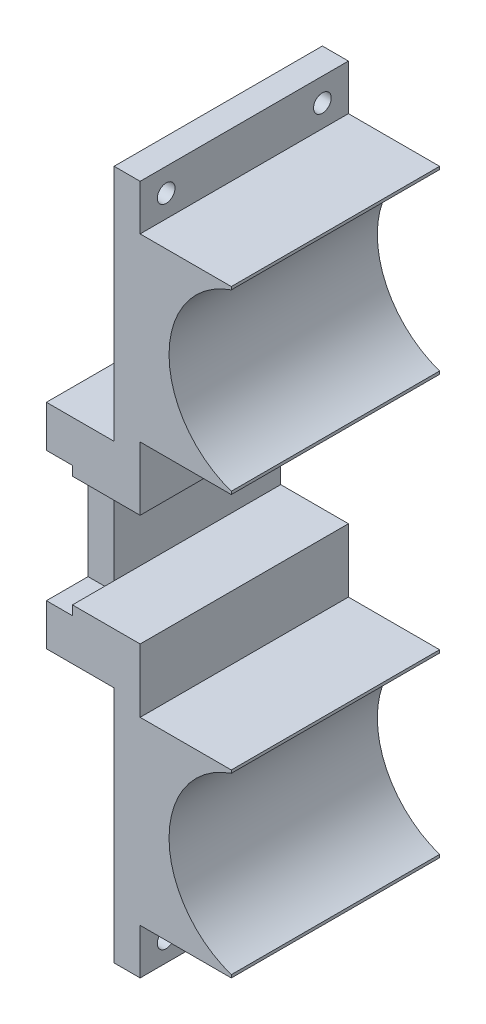
SolidWorks part; units mm, degrees
ref_plane "Płaszczyzna przednia" through (0, 0, 0) normal (0, 0, 1) x (1, 0, 0)
ref_plane "Płaszczyzna górna" through (0, 0, 0) normal (0, 1, 0) x (1, 0, 0)
ref_plane "Płaszczyzna prawa" through (0, 0, 0) normal (1, 0, 0) x (0, 0, -1)
sketch "Sketch1" plane through (0, 0, 0) normal (0, 0, 1) x (1, 0, 0)
  line L0 (0, 0) -> (0, -20.5)
  line L1 (0, -20.5) -> (13, -20.5)
  line L2 (13, -20.5) -> (13, -66.25)
  line L3 (13, -66.25) -> (18, -66.25)
  line L4 (18, -66.25) -> (18, -57.5)
  line L5 (18, -57.5) -> (37.5083, -57.5)
  line L7 (37.5083, -22.9) -> (18, -22.9)
  line L8 (18, -22.9) -> (18, -10.7)
  line L9 (18, -10.7) -> (5, -10.7)
  line L10 (5, -10.7) -> (5, 0)
  line L11 (5, 0) -> (0, 0)
  line L12 (35.5083, -22.9) -> (35.5083, -23.4571)
  line L13 (35.5083, -56.9429) -> (35.5083, -57.5)
  arc A0 (37.5083, -22.9) -> (37.5083, -57.5) centre (41.25, -40.2) ccw
  dimension "D10" = 19.5083
  dimension "D5" = 17.7
  dimension "D1" = 10.7
  dimension "D2" = 13
  dimension "D3" = 12.2
  dimension "D4" = 28.25
  dimension "D6" = 5
  dimension "D7" = 5
  dimension "D8" = 20.5
  dimension "D9" = 45.75
  dimension "D11" = 34.6
  dimension "D12" = 2
extrude "Boss-Extrude1" add sketch "Sketch1" along normal blind 40 contours A0 L12 L7 L8 L9 L10 L11 L0 L1 L2 L3 L4 L5 L13 region at (16.2423, -33.1042, 0)
mirror "Mirror1" about plane through (0, 0, 0) normal (0, 1, 0) of "Boss-Extrude1"
sketch "Sketch3" plane through (13, 0, 0) normal (-1, 0, 0) x (0, 0, 1)
  point P0 (35, -62.175)
  point P1 (5, -62.175)
  point P3 (35, 61.775)
  point P5 (5, 61.775)
hole_wizard "M3 Clearance Hole1" positions "Sketch3" profile "Sketch5" hole size "M3" standard "DIN" end condition up to next
sketch "Sketch5" plane through (13, -62.175, 35) normal (0, 1, 0) x (0, 0, 1)
  line L0 (0, 0) -> (0, 5)
  line L1 (0, 5) -> (1.7, 5)
  line L2 (1.7, 5) -> (1.7, 0)
  line L5 (1.7, 0) -> (0, 0)
  line L11 (0, -6.35) -> (0, 107.95) construction
  dimension "Thru Hole Dia." = 3.4
  dimension "Thru Hole Depth" = 5
sketch "Sketch6" plane through (0, 0, 40) normal (0, 0, -1) x (-1, 0, 0)
  line L0 (-5, -10.7) -> (-5, 10.7) construction
  line L1 (-5, 12.5) -> (0, 12.5)
  line L2 (-5, 12.5) -> (-5, -12.5)
  line L3 (-5, -12.5) -> (0, -12.5)
  line L4 (0, 12.5) -> (0, -12.5)
  line L5 (-2.5, -12.5) -> (-2.5, 12.5) construction
  line L6 (-5, 0) -> (0, 0) construction
  line L7 (0, 20.5) -> (0, -20.5) construction
  point P8 (-2.5, 0.2024)
  point P9 (0, 0)
  point P164 (-2.5, 0)
  dimension "D1" = 25
extrude "Cut-Extrude1" cut sketch "Sketch6" along normal blind 8
sketch "Sketch7" plane through (0, 0, 0) normal (-1, 0, 0) x (0, 0, 1)
  line L0 (40, -20.5) -> (0, -20.5) construction
  line L1 (0, 20.5) -> (40, 20.5)
  line L2 (0, 20.5) -> (0, -20.5)
  line L3 (0, -20.5) -> (40, -20.5)
  line L4 (40, 20.5) -> (40, -20.5)
  line L5 (20, -20.5) -> (20, 20.5) construction
  line L6 (0, 0) -> (40, 0) construction
  point P204 (20, 0)
  point P210 (36, -20.5)
  point P211 (40, -20.5)
hole_wizard "M3 Clearance Hole2" positions "Sketch7" profile "Sketch8" hole size "M3" standard "DIN" end condition up to next
sketch "Sketch8" plane through (0, 0, 20) normal (0, 1, 0) x (0, 0, 1)
  line L0 (0, 0) -> (0, 5)
  line L1 (0, 5) -> (1.7, 5)
  line L2 (1.7, 5) -> (1.7, 0)
  line L5 (1.7, 0) -> (0, 0)
  line L11 (0, -6.35) -> (0, 107.95) construction
  dimension "Thru Hole Dia." = 3.4
  dimension "Thru Hole Depth" = 5
